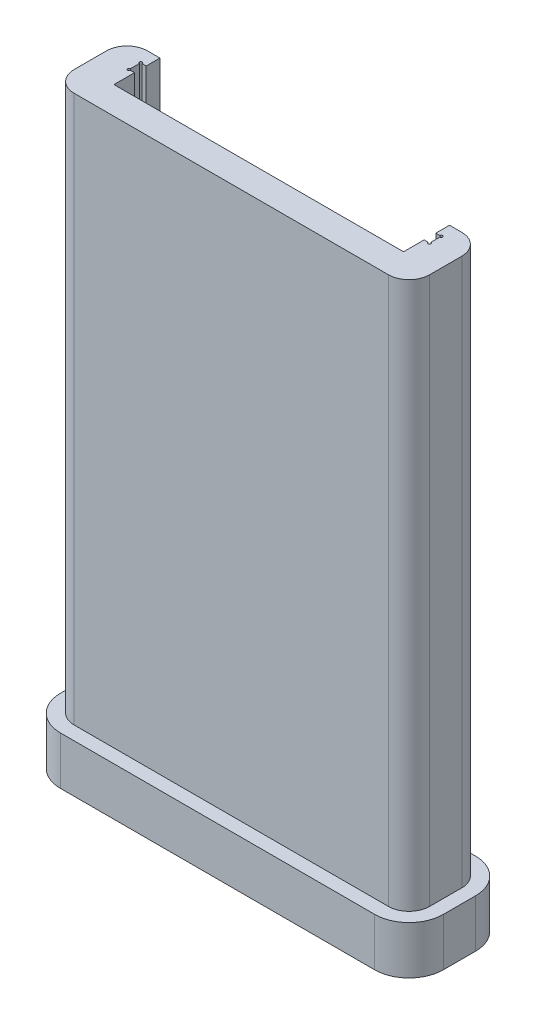
SolidWorks part; units mm, degrees
material "Melamine resin"
ref_plane "Front Plane" through (0, 0, 0) normal (0, 0, 1) x (1, 0, 0)
ref_plane "Top Plane" through (0, 0, 0) normal (0, 1, 0) x (1, 0, 0)
ref_plane "Right Plane" through (0, 0, 0) normal (1, 0, 0) x (0, 0, -1)
sketch "Sketch2" plane through (0, 0, 0) normal (0, 1, 0) x (1, 0, 0)
  line L1 (0, 0) -> (88.9, 0)
  line L2 (0, 0) -> (0, 152.4)
  line L3 (0, 152.4) -> (88.9, 152.4)
  line L10 (88.9, 152.4) -> (88.9, 0)
  dimension "D1" = 152.4
  dimension "D2" = 88.9
extrude "Boss-Extrude1" add sketch "Sketch2" along normal blind 5.9944 contours L3 L10 L1 L2
sketch "Sketch4" plane through (0, 5.9944, 0) normal (0, 1, 0) x (1, 0, 0)
  line L0 (0, 0) -> (0, 152.4) construction
  line L1 (0, 0) -> (88.9, 0) construction
  circle A0 centre (45.72, 109.8713) radius 2.7305
  circle A1 centre (45.72, 33.6713) radius 2.7305
  dimension "D3" = 5.461
  dimension "D4" = 5.461
  dimension "D1" = 76.2
  dimension "D2" = 45.72
  dimension "D5" = 33.6713
extrude "Cut-Extrude2" cut sketch "Sketch4" against normal through all both
sketch "Sketch5" plane through (0, 5.9944, 0) normal (0, 1, 0) x (1, 0, 0)
  line L0 (0, 152.4) -> (88.9, 152.4) construction
  line L1 (11.557, 16.129) -> (77.343, 16.129)
  line L2 (11.557, 16.129) -> (11.557, 2.54)
  line L3 (11.557, 2.54) -> (77.343, 2.54)
  line L4 (77.343, 16.129) -> (77.343, 2.54)
  line L5 (17.653, 7.62) -> (71.247, 7.62)
  line L6 (17.653, 7.62) -> (17.653, 16.129)
  line L7 (17.653, 16.129) -> (71.247, 16.129)
  line L8 (71.247, 7.62) -> (71.247, 16.129)
  line L9 (16.637, 13.589) -> (72.263, 13.589)
  line L10 (16.637, 13.589) -> (16.637, 11.43)
  line L11 (16.637, 11.43) -> (72.263, 11.43)
  line L12 (72.263, 13.589) -> (72.263, 11.43)
  line L13 (0, 0) -> (88.9, 0) construction
  circle A1 centre (16.637, 13.589) radius 0.254
  circle A2 centre (16.637, 11.43) radius 0.254
  circle A3 centre (72.263, 13.589) radius 0.254
  circle A4 centre (72.263, 11.43) radius 0.254
  point P16 (44.45, 152.4)
  point P17 (44.45, 16.129)
  dimension "D11" = 0.508
  dimension "D12" = 0.508
  dimension "D13" = 0.508
  dimension "D14" = 0.508
  dimension "D1" = 55.626
  dimension "D2" = 1.016
  dimension "D3" = 1.016
  dimension "D4" = 3.81
  dimension "D5" = 2.54
  dimension "D6" = 5.08
  dimension "D7" = 5.08
  dimension "D8" = 2.159
  dimension "D9" = 2.54
  dimension "D10" = 5.08
extrude "Boss-Extrude2" add sketch "Sketch5" along normal blind 101.6 contours L9 L12 L11 L8 L5 L6 L10 L1 L2 L3 L4 region at (44.45, 5.9944, -6.6224)
fillet "Fillet1" radius 3.81 4 edges at (11.557, 56.7944, -2.54) (11.557, 56.7944, -16.129) (77.343, 56.7944, -2.54) (77.343, 56.7944, -16.129)
sketch "Sketch7" plane through (0, 5.9944, 0) normal (0, 1, 0) x (1, 0, 0)
  line L0 (0, 0) -> (88.9, 0) construction
  line L1 (0, 152.4) -> (2.54, 152.4)
  line L2 (0, 152.4) -> (0, 0)
  line L3 (0, 0) -> (2.54, 0)
  line L4 (2.54, 152.4) -> (2.54, 0)
  dimension "D1" = 2.54
extrude "Cut-Extrude3" cut sketch "Sketch7" against normal through all both
sketch "Sketch11" plane through (0, 0, 0) normal (0, -1, 0) x (1, 0, 0)
  line L4 (2.54, 0) -> (2.54, -152.4)
  line L5 (2.54, -152.4) -> (88.9, -152.4)
  line L6 (88.9, -152.4) -> (88.9, 0)
  line L7 (88.9, 0) -> (2.54, 0)
  line L8 (2.54, 0) -> (2.54, -152.4)
  line L9 (2.54, -152.4) -> (88.9, -152.4)
  line L10 (88.9, -152.4) -> (88.9, 0)
  line L11 (88.9, 0) -> (2.54, 0)
  dimension "D1" = 0
extrude "Cut-Extrude4" cut sketch "Sketch11" against normal blind 6.35
sketch "Sketch12" plane through (0, 6.35, 0) normal (0, -1, 0) x (1, 0, 0)
  line L0 (17.653, -16.129) -> (71.247, -16.129)
  line L1 (71.247, -18.669) -> (73.533, -18.669)
  line L2 (79.883, -12.319) -> (79.883, -6.35)
  line L3 (73.533, 0) -> (15.367, 0)
  line L4 (9.017, -6.35) -> (9.017, -12.319)
  line L5 (15.367, -18.669) -> (17.653, -18.669)
  line L6 (17.653, -18.669) -> (71.247, -18.669)
  line L16 (72.263, -11.684) -> (72.263, -13.335)
  line L17 (72.009, -13.589) -> (71.247, -13.589)
  line L18 (71.247, -13.589) -> (71.247, -16.129)
  line L19 (71.247, -16.129) -> (73.533, -16.129)
  line L20 (77.343, -12.319) -> (77.343, -6.35)
  line L21 (73.533, -2.54) -> (15.367, -2.54)
  line L22 (11.557, -6.35) -> (11.557, -12.319)
  line L23 (15.367, -16.129) -> (17.653, -16.129)
  line L24 (17.653, -16.129) -> (17.653, -13.589)
  line L25 (17.653, -13.589) -> (16.891, -13.589)
  line L26 (16.637, -13.335) -> (16.637, -11.684)
  line L27 (16.891, -11.43) -> (17.653, -11.43)
  line L28 (17.653, -11.43) -> (17.653, -7.62)
  line L29 (17.653, -7.62) -> (71.247, -7.62)
  line L30 (71.247, -7.62) -> (71.247, -11.43)
  line L31 (71.247, -11.43) -> (72.009, -11.43)
  line L32 (72.263, -11.684) -> (72.263, -13.335)
  line L33 (72.009, -13.589) -> (71.247, -13.589)
  line L34 (71.247, -13.589) -> (71.247, -16.129)
  line L35 (71.247, -16.129) -> (73.533, -16.129)
  line L36 (77.343, -12.319) -> (77.343, -6.35)
  line L37 (73.533, -2.54) -> (15.367, -2.54)
  line L38 (11.557, -6.35) -> (11.557, -12.319)
  line L39 (15.367, -16.129) -> (17.653, -16.129)
  line L40 (17.653, -16.129) -> (17.653, -13.589)
  line L41 (17.653, -13.589) -> (16.891, -13.589)
  line L42 (16.637, -13.335) -> (16.637, -11.684)
  line L43 (16.891, -11.43) -> (17.653, -11.43)
  line L44 (17.653, -11.43) -> (17.653, -7.62)
  line L45 (17.653, -7.62) -> (71.247, -7.62)
  line L46 (71.247, -7.62) -> (71.247, -11.43)
  line L47 (71.247, -11.43) -> (72.009, -11.43)
  arc A0 (73.533, -18.669) -> (79.883, -12.319) centre (73.533, -12.319) ccw
  arc A1 (79.883, -6.35) -> (73.533, 0) centre (73.533, -6.35) ccw
  arc A2 (15.367, 0) -> (9.017, -6.35) centre (15.367, -6.35) ccw
  arc A3 (9.017, -12.319) -> (15.367, -18.669) centre (15.367, -12.319) ccw
  arc A4 (73.533, -16.129) -> (77.343, -12.319) centre (73.533, -12.319) ccw
  arc A5 (77.343, -6.35) -> (73.533, -2.54) centre (73.533, -6.35) ccw
  arc A6 (15.367, -2.54) -> (11.557, -6.35) centre (15.367, -6.35) ccw
  arc A7 (11.557, -12.319) -> (15.367, -16.129) centre (15.367, -12.319) ccw
  arc A8 (73.533, -16.129) -> (77.343, -12.319) centre (73.533, -12.319) ccw
  arc A9 (77.343, -6.35) -> (73.533, -2.54) centre (73.533, -6.35) ccw
  arc A10 (15.367, -2.54) -> (11.557, -6.35) centre (15.367, -6.35) ccw
  arc A11 (11.557, -12.319) -> (15.367, -16.129) centre (15.367, -12.319) ccw
  arc A17 (16.637, -13.335) -> (16.891, -13.589) centre (16.637, -13.589) ccw
  arc A18 (16.637, -13.335) -> (16.891, -13.589) centre (16.637, -13.589) ccw
  arc A22 (72.009, -13.589) -> (72.263, -13.335) centre (72.263, -13.589) ccw
  arc A23 (72.009, -13.589) -> (72.263, -13.335) centre (72.263, -13.589) ccw
  arc A24 (16.891, -11.43) -> (16.637, -11.684) centre (16.637, -11.43) ccw
  arc A25 (16.891, -11.43) -> (16.637, -11.684) centre (16.637, -11.43) ccw
  arc A26 (72.263, -11.684) -> (72.009, -11.43) centre (72.263, -11.43) ccw
  arc A27 (72.263, -11.684) -> (72.009, -11.43) centre (72.263, -11.43) ccw
  line M22 (72.263, -11.684) -> (72.263, -13.335)
  line M23 (72.009, -13.589) -> (71.247, -13.589)
  line M24 (71.247, -13.589) -> (71.247, -16.129)
  line M25 (71.247, -16.129) -> (73.533, -16.129)
  arc M26 (73.533, -16.129) -> (77.343, -12.319) centre (73.533, -12.319) ccw
  line M27 (77.343, -12.319) -> (77.343, -6.35)
  arc M28 (77.343, -6.35) -> (73.533, -2.54) centre (73.533, -6.35) ccw
  line M29 (73.533, -2.54) -> (15.367, -2.54)
  arc M30 (15.367, -2.54) -> (11.557, -6.35) centre (15.367, -6.35) ccw
  line M31 (11.557, -6.35) -> (11.557, -12.319)
  arc M32 (11.557, -12.319) -> (15.367, -16.129) centre (15.367, -12.319) ccw
  line M33 (15.367, -16.129) -> (17.653, -16.129)
  line M34 (17.653, -16.129) -> (17.653, -13.589)
  line M35 (17.653, -13.589) -> (16.891, -13.589)
  line M36 (16.637, -13.335) -> (16.637, -11.684)
  line M37 (16.891, -11.43) -> (17.653, -11.43)
  line M38 (17.653, -11.43) -> (17.653, -7.62)
  line M39 (17.653, -7.62) -> (71.247, -7.62)
  line M40 (71.247, -7.62) -> (71.247, -11.43)
  line M41 (71.247, -11.43) -> (72.009, -11.43)
  dimension "D1" = 0
  dimension "D2" = 2.54
extrude "Boss-Extrude3" add sketch "Sketch12" along normal blind 8.89 contours L4 A3 L5 L6 L1 A0 L2 A1 L3 A2 L0 M33 M32 M31 M30 M29 M28 M27 M26 M25 | M41 M22 M23 M24 M25 M26 M27 M28 M29 M30 M31 M32 M33 M34 M35 M36 M37 M38 M39 M40 | L0 M34 M24 M23 M22 M41 M40 M39 M38 M37 M36 M35 region at (44.45, 6.35, -11.8814) region at (44.45, 6.35, -6.542) region at (44.45, 6.35, -17.9362)
sketch "Sketch13" plane through (0, -2.54, 0) normal (0, -1, 0) x (1, 0, 0)
  line L0 (19.05, -9.3345) -> (69.85, -9.3345) construction
  line L1 (73.533, 0) -> (15.367, 0) construction
  line L2 (79.883, -12.319) -> (79.883, -6.35) construction
  circle A0 centre (19.05, -9.3345) radius 2.7305
  circle A1 centre (69.85, -9.3345) radius 2.7305
  point P6 (44.45, 0)
  point P7 (44.45, -9.3345)
  point P10 (79.883, -9.3345)
  dimension "D1" = 5.461
  dimension "D2" = 5.461
  dimension "D3" = 50.8
extrude "Cut-Extrude5" cut sketch "Sketch13" against normal blind 6.35
equation "\"threaded_insert_hole\"=0.1472"
equation "\"th\"=1.25249"
